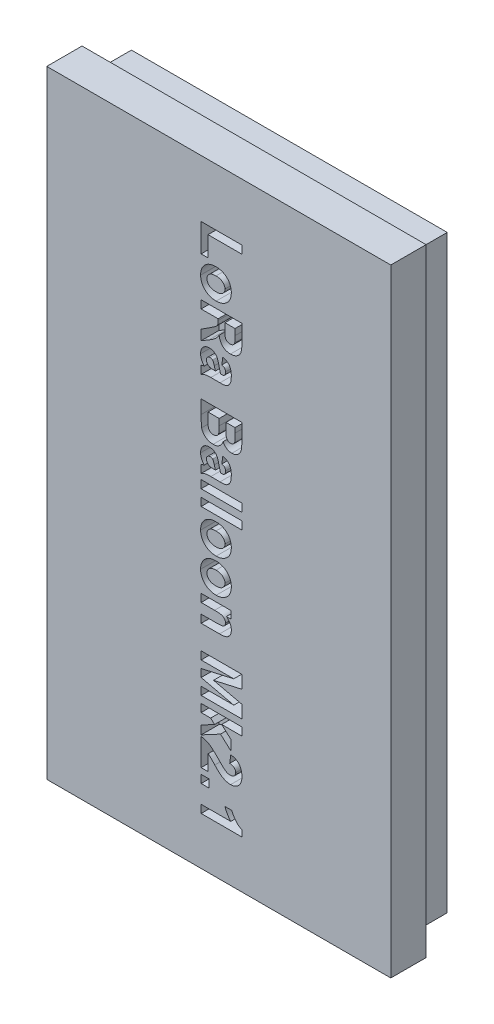
SolidWorks part; units mm, degrees
ref_plane "Front Plane" through (0, 0, 0) normal (0, 0, 1) x (1, 0, 0)
ref_plane "Top Plane" through (0, 0, 0) normal (0, 1, 0) x (1, 0, 0)
ref_plane "Right Plane" through (0, 0, 0) normal (1, 0, 0) x (0, 0, -1)
sketch "Sketch1" plane through (0, 0, 0) normal (0, 0, 1) x (1, 0, 0)
  line L1 (0, 0) -> (39, 0)
  line L2 (0, 0) -> (0, 70)
  line L3 (0, 70) -> (39, 70)
  line L4 (39, 0) -> (39, 70)
  dimension "D1" = 70
  dimension "D2" = 39
extrude "Boss-Extrude1" add sketch "Sketch1" along normal blind 4
sketch "Sketch2" plane through (0, 0, 0) normal (0, 0, -1) x (-1, 0, 0)
  line L0 (-39, 0) -> (-39, 70) construction
  line L1 (-37.4, 68.4) -> (-35.6, 68.4)
  line L2 (-37.4, 68.4) -> (-37.4, 1.6)
  line L3 (-37.4, 1.6) -> (-35.6, 1.6)
  line L4 (-35.6, 68.4) -> (-35.6, 1.6)
  line L5 (0, 0) -> (-39, 0) construction
  line L6 (0, 70) -> (0, 0) construction
  line L7 (-35.6, 1.6) -> (-1.6, 1.6)
  line L8 (-35.6, 1.6) -> (-35.6, 3.4)
  line L9 (-35.6, 3.4) -> (-1.6, 3.4)
  line L10 (-1.6, 1.6) -> (-1.6, 3.4)
  line L12 (-39, 70) -> (0, 70) construction
  line L13 (-39, 35) -> (0, 35) construction
  line L14 (-19.5, 70) -> (-19.5, 0) construction
  line L15 (-35.6, 66.6) -> (-1.6, 66.6)
  line L16 (-1.6, 68.4) -> (-1.6, 66.6)
  line L17 (-35.6, 68.4) -> (-1.6, 68.4)
  line L18 (-35.6, 68.4) -> (-35.6, 66.6)
  line L19 (-1.6, 1.6) -> (-3.4, 1.6)
  line L20 (-3.4, 68.4) -> (-3.4, 1.6)
  line L21 (-1.6, 68.4) -> (-3.4, 68.4)
  line L22 (-1.6, 68.4) -> (-1.6, 1.6)
  dimension "D1" = 1.6
  dimension "D2" = 1.8
  dimension "D3" = 1.6
  dimension "D4" = 1.8
extrude "Boss-Extrude2" add sketch "Sketch2" along normal blind 4 contours L4 L1 L2 L3 | L22 L15 L20 L9 | L20 L9 L4 L7 | L9 L20 L7 L10 | L17 L20 L15 L16 | L20 L17 L4 L15 region at (36.5, 35, 0) region at (19.5, 67.5, 0) region at (2.5, 67.5, 0) region at (19.5, 2.5, 0) region at (2.5, 35, 0) region at (2.5, 2.5, 0)
sketch "Sketch3" plane through (0, 0, 4) normal (0, 0, 1) x (1, 0, 0)
  line L0 (17.5, 0) -> (17.5, 64) construction
  line L4 (0, 0) -> (39, 0) construction
  line L6 (0, 70) -> (0, 0) construction
  text T0 "<b>LoRa Balloon Mk2.1</b>" font "Arial Narrow" height in points 18
  dimension "D1" = 17.5
  dimension "D2" = 64
extrude "Cut-Extrude1" cut sketch "Sketch3" against normal blind 2
